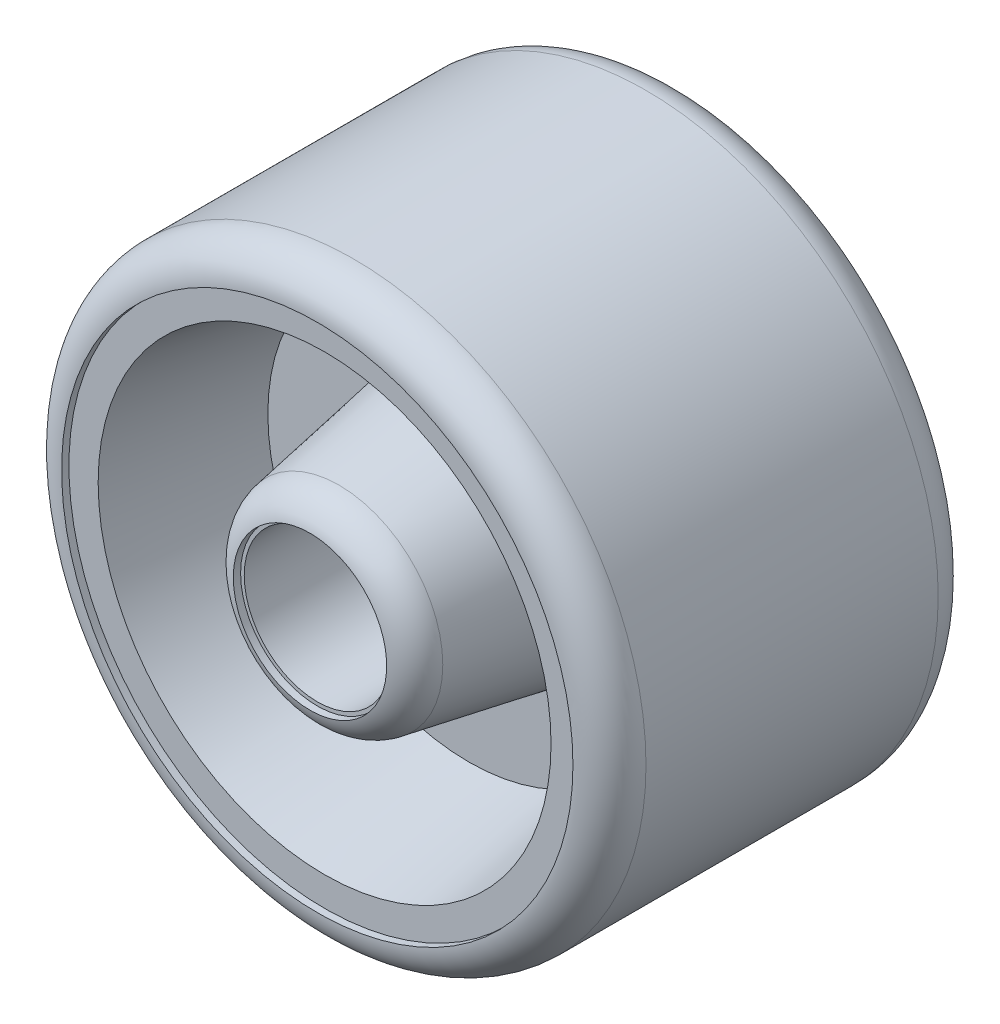
SolidWorks part; units mm, degrees
ref_plane "Front Plane" through (0, 0, 0) normal (0, 0, 1) x (1, 0, 0)
ref_plane "Top Plane" through (0, 0, 0) normal (0, 1, 0) x (1, 0, 0)
ref_plane "Right Plane" through (0, 0, 0) normal (1, 0, 0) x (0, 0, -1)
sketch "Sketch1" plane through (0, 0, 0) normal (0, 0, 1) x (1, 0, 0)
  circle A0 centre (0, 0) radius 8
  circle A1 centre (0, 0) radius 7
  dimension "D1" = 16
extrude "Boss-Extrude1" add sketch "Sketch1" along normal mid plane 10
fillet "Fillet1" radius 1 2 edges at (8, 0, -5) (8, 0, 5)
sketch "Sketch2" plane through (0, 0, 0) normal (0, 1, 0) x (1, 0, 0)
  line L0 (0, 0) -> (-11.7003, 0) construction
  line L1 (0, 5) -> (0, -5)
  line L2 (0, -5) -> (-2.1, -5)
  line L3 (-2.1, -5) -> (-2.1, -5.2)
  line L4 (-2.1, -5.2) -> (-2.7, -5.2)
  line L5 (-2.7, -5.2) -> (-3.467, -0.85)
  line L6 (-3.467, -0.85) -> (-5.5035, -0.85)
  line L7 (-5.5035, -0.85) -> (-6.2, -4.8)
  line L8 (-6.2, -4.8) -> (-7, -4.8)
  line L9 (-7, -4.8) -> (-7, 4.8)
  line L10 (-6.2, 4.8) -> (-7, 4.8)
  line L11 (-5.5035, 0.85) -> (-6.2, 4.8)
  line L12 (-3.467, 0.85) -> (-5.5035, 0.85)
  line L13 (-2.7, 5.2) -> (-3.467, 0.85)
  line L14 (-2.1, 5.2) -> (-2.7, 5.2)
  line L15 (-2.1, 5) -> (-2.1, 5.2)
  line L16 (0, 5) -> (-2.1, 5)
  point P4 (0, 0)
  point P14 (-7, 0)
  dimension "D1" = 2.1
  dimension "D2" = 0.6
  dimension "D3" = 7
  dimension "D4" = 0.8
  dimension "D5" = 100
  dimension "D6" = 100
  dimension "D7" = 5
  dimension "D8" = 4.8
  dimension "D9" = 1.7
revolve "Revolve1" add sketch "Sketch2" angle 360 about L1
sketch "Sketch3" plane through (0, 0, 0) normal (0, 1, 0) x (1, 0, 0)
  line L0 (-2.5467, 2.55) -> (-2.5467, 0.85)
  line L1 (3.467, 0.85) -> (-3.467, 0.85) construction
  line L2 (-2.5467, 0.85) -> (-4.5467, 0.85)
  line L3 (5.5035, 0.85) -> (-5.5035, 0.85) construction
  line L4 (-4.5467, 0.85) -> (-4.5467, 1.15)
  line L5 (-4.5467, 1.15) -> (-2.8467, 2.55)
  line L6 (-2.8467, 2.55) -> (-2.5467, 2.55)
  dimension "D1" = 1.7
  dimension "D2" = 2
  dimension "D3" = 0.3
  dimension "D4" = 0.3
extrude "Boss-Extrude2" add sketch "Sketch3" along normal mid plane 1.7
sketch "Sketch4" plane through (0, 0, -5) normal (0, 0, -1) x (-1, 0, 0)
  circle A0 centre (0, 0) radius 2
extrude "Cut-Extrude1" cut sketch "Sketch4" against normal through all
fillet "Fillet3" radius 1 1 edges at (-2.7, 0, 5.2)
fillet "Fillet4" radius 1 1 edges at (-2.7, 0, -5.2)
